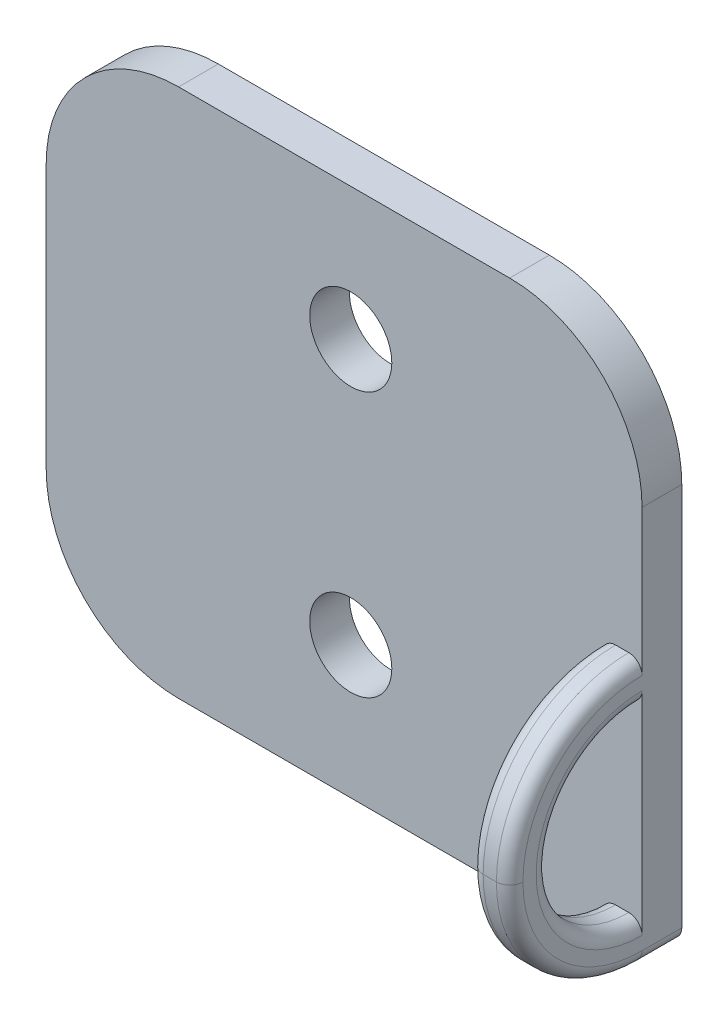
SolidWorks part; units mm, degrees
ref_plane "Front Plane" through (0, 0, 0) normal (0, 0, 1) x (1, 0, 0)
ref_plane "Top Plane" through (0, 0, 0) normal (0, 1, 0) x (1, 0, 0)
ref_plane "Right Plane" through (0, 0, 0) normal (1, 0, 0) x (0, 0, -1)
sketch "Sketch1" plane through (0, 0, 0) normal (0, 0, 1) x (1, 0, 0)
  line L0 (23, 40) -> (23, 0) construction
  line L1 (10, 0) -> (45, 0)
  line L2 (0, 10) -> (0, 30)
  line L3 (10, 40) -> (35, 40)
  line L4 (45, 0) -> (45, 30)
  circle A0 centre (23, 30) radius 3.1
  circle A1 centre (23, 10) radius 3.1
  arc A2 (10, 0) -> (0, 10) centre (10, 10) cw
  arc A3 (35, 40) -> (45, 30) centre (35, 30) cw
  arc A4 (0, 30) -> (10, 40) centre (10, 30) cw
  point P13 (0, 0)
  point P18 (0, 40)
  point P21 (23, 29.6199)
  dimension "D4" = 10
  dimension "D5" = 6.2
  dimension "D1" = 45
  dimension "D2" = 40
  dimension "D3" = 22
  dimension "D6" = 10
  dimension "D7" = 20
extrude "Boss-Extrude1" add sketch "Sketch1" along normal blind 3
sketch "Sketch2" plane through (0, 0, 3) normal (0, 0, 1) x (1, 0, 0)
  line L1 (45, 0) -> (42, 0)
  line L2 (45, 0) -> (45, 20)
  line L3 (45, 20) -> (42, 20)
  line L4 (42, 0) -> (42, 20)
  dimension "D1" = 3
  dimension "D2" = 20
extrude "Boss-Extrude2" add sketch "Sketch2" along normal blind 10
fillet "Fillet1" radius 10 2 edges at (43.5, 0, 13) (43.5, 20, 13)
sketch "Sketch3" plane through (42, 0, 0) normal (-1, 0, 0) x (0, 0, 1)
  line L0 (3, 20) -> (3, 0) construction
  line L1 (3, 17) -> (3, 3)
  arc A0 (3, 17) -> (3, 3) centre (3, 10) cw
  arc A1 (13, 10) -> (3, 20) centre (3, 10) ccw construction
  dimension "D1" = 3
extrude "Cut-Extrude1" cut sketch "Sketch3" against normal through all
fillet "Fillet2" radius 1 7 edges at (45, 0, 1.5) (45, 2.9289, 10.0711) (42, 2.9289, 10.0711) (45, 10, 10) (45, 17.0711, 10.0711) (42, 17.0711, 10.0711) (42, 10, 10)
